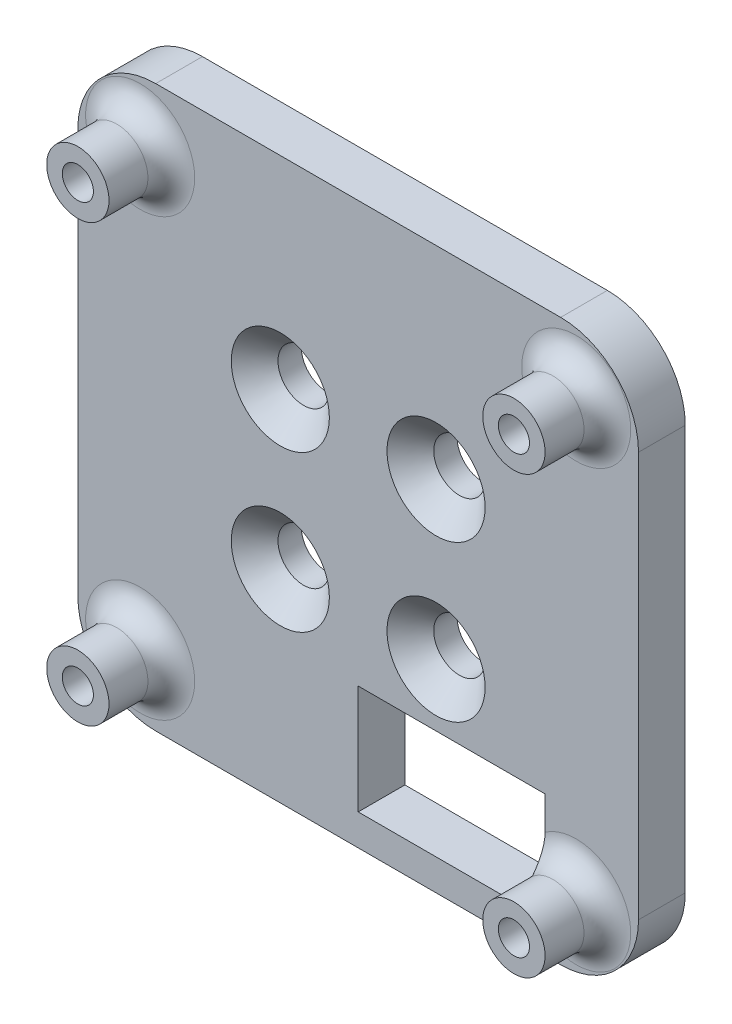
SolidWorks part; units mm, degrees
ref_plane "Спереди" through (0, 0, 0) normal (0, 0, 1) x (1, 0, 0)
ref_plane "Сверху" through (0, 0, 0) normal (0, 1, 0) x (1, 0, 0)
ref_plane "Справа" through (0, 0, 0) normal (1, 0, 0) x (0, 0, -1)
sketch "Эскиз1" plane through (0, 0, 0) normal (0, 0, 1) x (1, 0, 0)
  line L1 (-18, 18) -> (18, 18)
  line L2 (-18, 18) -> (-18, -18)
  line L3 (-18, -18) -> (18, -18)
  line L4 (18, 18) -> (18, -18)
  line L5 (-18, 18) -> (18, -18) construction
  line L6 (-18, -18) -> (18, 18) construction
  line L7 (-14, 14) -> (14, 14) construction
  line L8 (-14, 14) -> (-14, -14) construction
  line L9 (-14, -14) -> (14, -14) construction
  line L10 (14, 14) -> (14, -14) construction
  line L11 (-14, 14) -> (14, -14) construction
  line L12 (-14, -14) -> (14, 14) construction
  line L13 (-19, 19) -> (19, 19) construction
  line L14 (-19, 19) -> (-19, -19) construction
  line L15 (-19, -19) -> (19, -19) construction
  line L16 (19, 19) -> (19, -19) construction
  line L17 (-19, 19) -> (19, -19) construction
  line L18 (-19, -19) -> (19, 19) construction
  line L19 (0, -9) -> (12, -9)
  line L20 (0, -9) -> (0, -16)
  line L21 (0, -16) -> (12, -16)
  line L22 (12, -9) -> (12, -16)
  line L23 (0, -9) -> (12, -16) construction
  line L24 (0, -16) -> (12, -9) construction
  line L25 (-5, 5) -> (5, 5) construction
  line L26 (-5, 5) -> (-5, -5) construction
  line L27 (-5, -5) -> (5, -5) construction
  line L28 (5, 5) -> (5, -5) construction
  line L29 (-5, 5) -> (5, -5) construction
  line L30 (-5, -5) -> (5, 5) construction
  circle A0 centre (-14, 14) radius 1
  circle A1 centre (14, 14) radius 1
  circle A2 centre (14, -14) radius 1
  circle A3 centre (-14, -14) radius 1
  circle A4 centre (-5, 5) radius 1.65
  circle A5 centre (5, 5) radius 1.65
  circle A6 centre (5, -5) radius 1.65
  circle A7 centre (-5, -5) radius 1.65
  point P0 (0, 0)
  point P6 (0, 0)
  point P15 (0, 0)
  point P20 (6, -12.5)
  point P28 (0, 0)
  dimension "D2" = 2
  dimension "D10" = 3.3
  dimension "D1" = 36
  dimension "D3" = 28
  dimension "D4" = 38
  dimension "D5" = 12
  dimension "D6" = 7
  dimension "D7" = 6
  dimension "D8" = 2
  dimension "D9" = 10
extrude "Основа" add sketch "Эскиз1" along normal blind 3 contours L4 L1 L2 L3 A7 A6 A5 A4 A3 A2 A1 A0 L19 L22 L21 L20 | L22 L19 L20 L21 region at (-0.4325, 0.9011, 0) region at (6, -12.5, 0)
sketch "Эскиз2" plane through (0, 0, 3) normal (0, 0, 1) x (1, 0, 0)
  circle A0 centre (-14, 14) radius 2
  circle A1 centre (-14, 14) radius 1
  circle A4 centre (14, 14) radius 2
  circle A5 centre (14, 14) radius 1
  circle A6 centre (14, -14) radius 2
  circle A7 centre (14, -14) radius 1
  circle A8 centre (-14, -14) radius 2
  circle A9 centre (-14, -14) radius 1
  circle A10 centre (-14, 14) radius 1 construction
  point P6 (0.9994, 0)
  point P18 (0, 0)
  dimension "D1" = 4
  dimension "D2" = 4
extrude "Стойки" add sketch "Эскиз2" along normal blind 4
fillet "Скругление1" radius 5 4 edges at (-18, -18, 1.5) (18, -18, 1.5) (18, 18, 1.5) (-18, 18, 1.5)
fillet "Скругление3" radius 1.5 4 edges at (-12, -14, 3) (16, -14, 3) (16, 14, 3) (-12, 14, 3)
chamfer "Фаска1" distance 1.5 angle 45 4 edges at (-3.35, -5, 3) (6.65, -5, 3) (6.65, 5, 3) (-3.35, 5, 3)
extrude "Вырез под шлейф" cut sketch "Эскиз1<3>" along normal up to next contours L22 L19 L20 L21 region at (6, -12.5, 0)
sketch "Эскиз1<3>" plane through (0, 0, 0) normal (0, 0, 1) x (1, 0, 0) same geometry as "Эскиз1"
